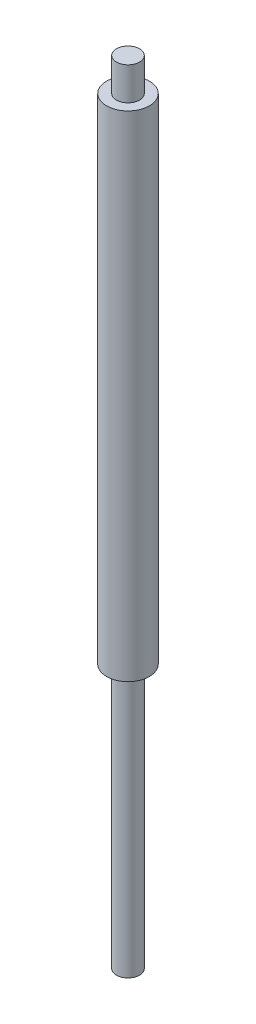
SolidWorks part; units mm, degrees
ref_plane "Front Plane" through (0, 0, 0) normal (0, 0, 1) x (1, 0, 0)
ref_plane "Top Plane" through (0, 0, 0) normal (0, 1, 0) x (1, 0, 0)
ref_plane "Right Plane" through (0, 0, 0) normal (1, 0, 0) x (0, 0, -1)
sketch "Sketch1" plane through (0, 0, 0) normal (0, 1, 0) x (1, 0, 0)
  circle A0 centre (0, 0) radius 0.35
  dimension "D1" = 0.7
sketch "Sketch2" plane through (0, 0, 0) normal (0, 1, 0) x (1, 0, 0)
  circle A0 centre (0, 0) radius 0.65
  dimension "D1" = 1.3
sketch "Sketch3" plane through (0, 0, 0) normal (1, 0, 0) x (0, 0, -1)
  line L0 (0.35, 0) -> (-0.35, 0) construction
  line L1 (-0.35, 0) -> (-0.65, 0) construction
  line L2 (0.35, 0) -> (0.65, 0) construction
  line L3 (0, 0) -> (0, 15) construction
  line L4 (0, 0) -> (0, -8) construction
  line L11 (0.65, 15) -> (-0.65, 15)
  line L12 (-0.65, 15) -> (-0.65, 0)
  line L13 (-0.65, 0) -> (-0.35, 0)
  line L14 (-0.35, 0) -> (-0.35, -8)
  line L15 (-0.35, -8) -> (0.35, -8)
  line L16 (0.35, -8) -> (0.35, 0)
  line L17 (0.35, 0) -> (0.65, 0)
  line L18 (0.65, 0) -> (0.65, 15)
  dimension "D1" = 8
  dimension "D2" = 15
extrude "Boss-Extrude1" add sketch "Sketch1" against normal up to vertex (8 mm away) up to point (0, -8, -0.35)
extrude "Boss-Extrude2" add sketch "Sketch2" along normal up to vertex (15 mm away) up to point (0, 15, -0.65)
sketch "Sketch4" plane through (0, 15, 0) normal (0, 1, 0) x (1, 0, 0)
  circle A0 centre (0, 0) radius 0.35 construction
  circle A1 centre (0, 0) radius 0.35
extrude "Boss-Extrude3" add sketch "Sketch4" along normal blind 1
